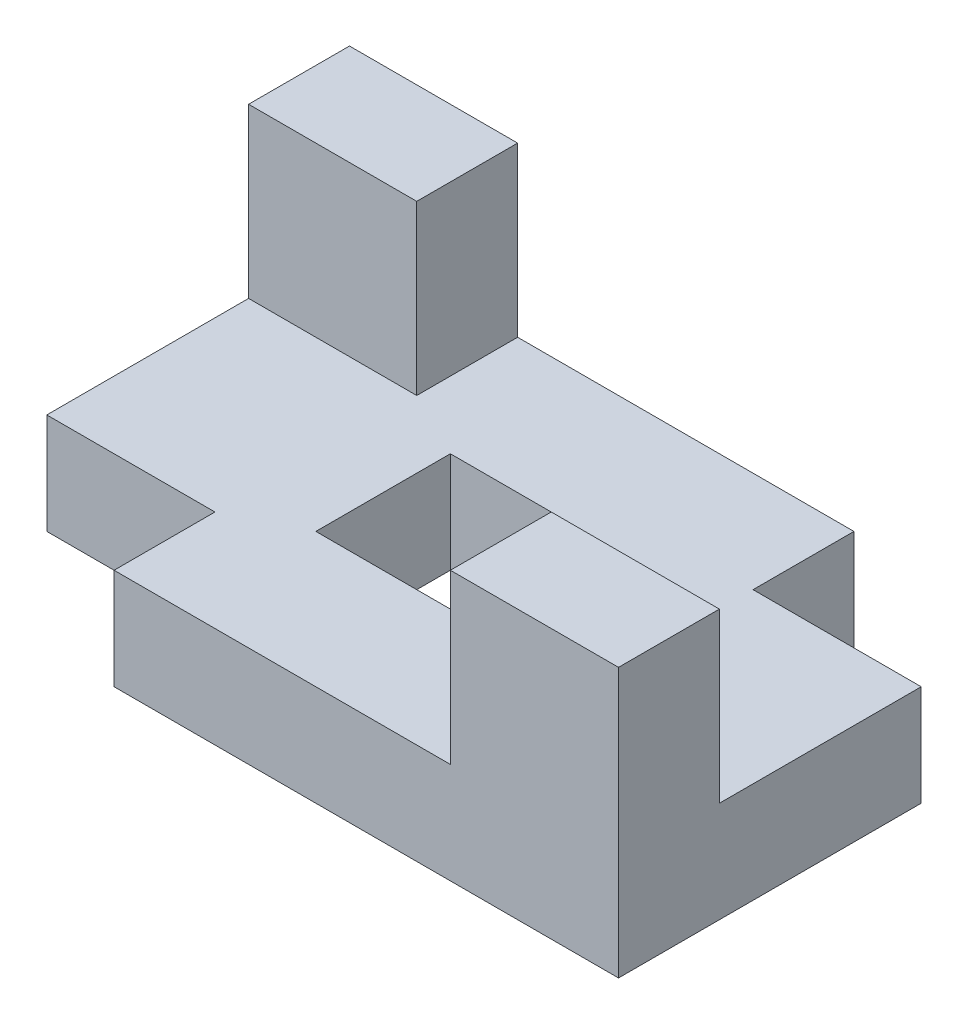
SolidWorks part; units mm, degrees
ref_plane "Front Plane" through (0, 0, 0) normal (0, 0, 1) x (1, 0, 0)
ref_plane "Top Plane" through (0, 0, 0) normal (0, 1, 0) x (1, 0, 0)
ref_plane "Right Plane" through (0, 0, 0) normal (1, 0, 0) x (0, 0, -1)
sketch "Sketch1" plane through (0, 0, 0) normal (0, 1, 0) x (1, 0, 0)
  line L1 (-50, 30) -> (50, 30)
  line L2 (-50, 30) -> (-50, -30)
  line L3 (-50, -30) -> (50, -30)
  line L4 (50, 30) -> (50, -30)
  dimension "D1" = 60
  dimension "D2" = 100
  dimension "D3" = 30
  dimension "D4" = 50
extrude "Boss-Extrude1" add sketch "Sketch1" along normal blind 15 contours L2 L1 L4 L3
sketch "Sketch3" plane through (0, 15, 0) normal (0, 1, 0) x (1, 0, 0)
  line L1 (-50, 30) -> (-25, 30)
  line L2 (-50, 30) -> (-50, 15)
  line L3 (-50, 15) -> (-25, 15)
  line L4 (-25, 30) -> (-25, 15)
  line L5 (50, -30) -> (25, -30)
  line L6 (50, -30) -> (50, -15)
  line L7 (50, -15) -> (25, -15)
  line L8 (25, -30) -> (25, -15)
  dimension "D1" = 15
  dimension "D2" = 25
extrude "Boss-Extrude3" add sketch "Sketch3" along normal blind 25 contours L4 L3 L2 L1
extrude "Boss-Extrude5" add sketch "Sketch3<6>" along normal blind 25 contours L8 L7 L6 L5
sketch "Sketch3<6>" plane through (0, 15, 0) normal (0, 1, 0) x (1, 0, 0) same geometry as "Sketch3"
sketch "Sketch6" plane through (0, 15, 0) normal (0, 1, 0) x (1, 0, 0)
  line L0 (-50, 15) -> (-25, 15) construction
  line L1 (50, 30) -> (25, 30)
  line L2 (50, 30) -> (50, 15)
  line L3 (50, 15) -> (25, 15)
  line L4 (25, 30) -> (25, 15)
  line L5 (-50, -30) -> (-25, -30)
  line L6 (-50, -30) -> (-50, -15)
  line L7 (-50, -15) -> (-25, -15)
  line L8 (-25, -30) -> (-25, -15)
  line L9 (-25, 30) -> (-25, 15) construction
extrude "Cut-Extrude1" cut sketch "Sketch6" against normal through all contours L7 L8 L5 L6
extrude "Cut-Extrude2" cut sketch "Sketch6<3>" against normal through all
sketch "Sketch6<3>" plane through (0, 15, 0) normal (0, 1, 0) x (1, 0, 0) same geometry as "Sketch6"
sketch "Sketch7" plane through (0, 15, 0) normal (0, 1, 0) x (1, 0, 0)
  line L0 (-50, 15) -> (-50, -15) construction
  line L1 (-15, 10) -> (15, 10)
  line L2 (-15, 10) -> (-15, -10)
  line L3 (-15, -10) -> (15, -10)
  line L4 (15, 10) -> (15, -10)
  line L5 (-25, -30) -> (25, -30) construction
  dimension "D1" = 20
  dimension "D2" = 30
  dimension "D3" = 35
  dimension "D4" = 20
extrude "Cut-Extrude3" cut sketch "Sketch7" against normal through all
sketch "Sketch8" plane through (0, 0, -15) normal (0, 0, 1) x (1, 0, 0)
  line L0 (-22.9804, 34.5644) -> (-22.9804, 41.3174)
